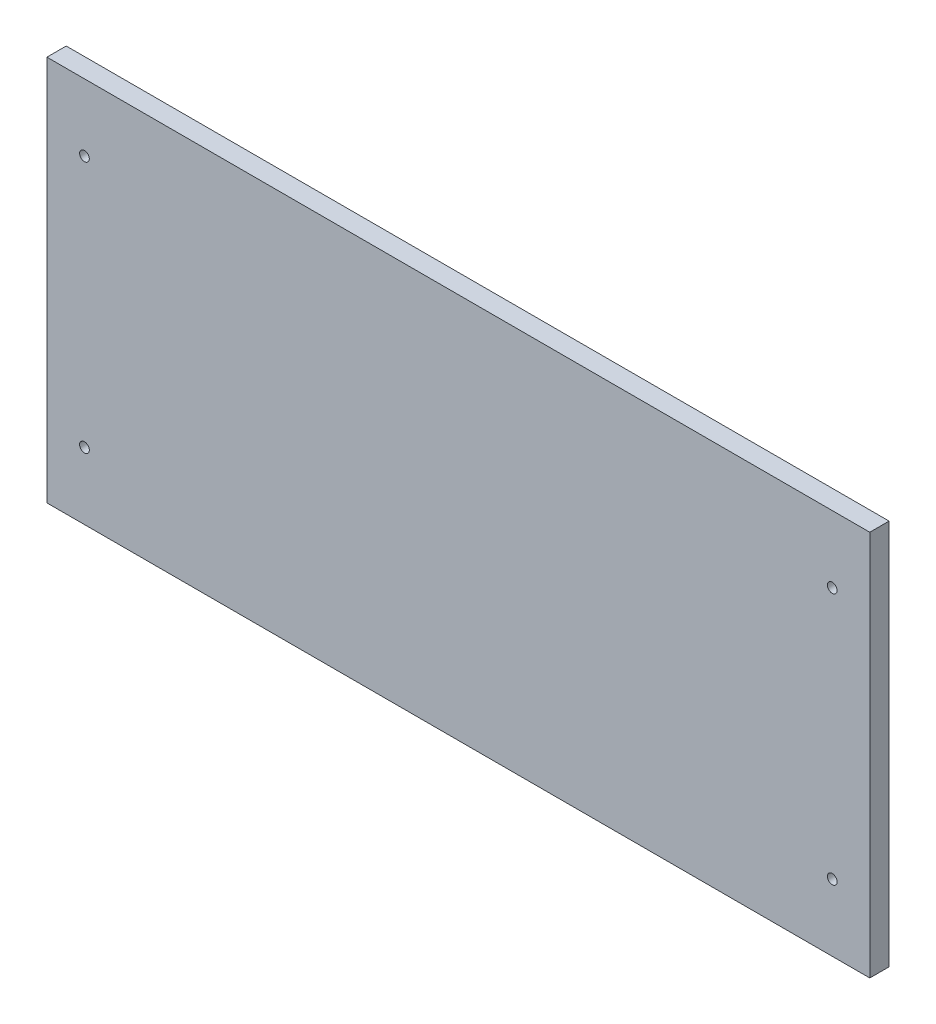
SolidWorks part; units mm, degrees
ref_plane "Front Plane" through (0, 0, 0) normal (0, 0, 1) x (1, 0, 0)
ref_plane "Top Plane" through (0, 0, 0) normal (0, 1, 0) x (1, 0, 0)
ref_plane "Right Plane" through (0, 0, 0) normal (1, 0, 0) x (0, 0, -1)
sketch "Sketch1" plane through (0, 0, 0) normal (0, 0, 1) x (1, 0, 0)
  line L0 (135.35, 127) -> (135.35, 0) construction
  line L1 (0, 0) -> (270.7, 0)
  line L2 (0, 0) -> (0, 127)
  line L3 (0, 127) -> (270.7, 127)
  line L4 (270.7, 0) -> (270.7, 127)
  line L5 (0, 63.5) -> (270.7, 63.5) construction
  circle A3 centre (12.35, 105) radius 1.6
  circle A7 centre (258.35, 105) radius 1.6
  circle A8 centre (258.35, 22) radius 1.6
  circle A9 centre (12.35, 22) radius 1.6
  dimension "D11" = 3.2
  dimension "D1" = 127
  dimension "D2" = 270.7
  dimension "D12" = 12.35
  dimension "D13" = 22
extrude "Wall" add sketch "Sketch1" along normal blind 6.35
sketch "Sketch2" plane through (0, 0, 6.35) normal (0, 0, 1) x (1, 0, 0)
  line L0 (135.35, 127) -> (135.35, 98.425) construction
  line L1 (270.7, 127) -> (0, 127) construction
  line L2 (135.35, 98.425) -> (66.6667, 98.425) construction
  line L3 (135.35, 98.425) -> (204.0333, 98.425) construction
  line L4 (0, 127) -> (0, 0) construction
  circle A0 centre (135.35, 98.425) radius 3.9687
  circle A1 centre (66.6667, 98.425) radius 3.9688
  circle A2 centre (204.0333, 98.425) radius 3.9687
  dimension "D2" = 7.9375
  dimension "D1" = 28.575
  dimension "D3" = 66.6667
extrude "RodSupportCutouts" [suppressed] cut sketch "Sketch2" against normal up to next
sketch "Sketch3" plane through (0, 0, 6.35) normal (0, 0, 1) x (1, 0, 0)
  line L1 (25.4, 88.9) -> (245.3, 88.9)
  line L2 (25.4, 88.9) -> (25.4, 114.3)
  line L3 (25.4, 114.3) -> (245.3, 114.3)
  line L4 (245.3, 88.9) -> (245.3, 114.3)
  line L5 (25.4, 88.9) -> (245.3, 114.3) construction
  line L6 (25.4, 114.3) -> (245.3, 88.9) construction
  line L7 (270.7, 127) -> (0, 127) construction
  line L8 (0, 127) -> (0, 0) construction
  point P0 (135.35, 101.6)
  point P9 (135.35, 127)
  dimension "D1" = 25.4
  dimension "D2" = 25.4
  dimension "D3" = 25.4
extrude "CannulaLargeCutout" [suppressed] cut sketch "Sketch3" against normal up to next
sketch "Sketch4" [suppressed] plane through (0, 0, 9.525) normal (0, 0, 1) x (1, 0, 0)
  line L0 (6, 103.5) -> (194, 103.5) construction
  line L1 (6, 105) -> (6, 22) construction
  line L2 (194, 105) -> (194, 22) construction
  line L3 (200, 127) -> (0, 127) construction
  line L4 (0, 127) -> (0, 0) construction
  circle A0 centre (60, 103.5) radius 6.35
  circle A1 centre (20, 103.5) radius 6.35
  circle A2 centre (100, 103.5) radius 6.35
  circle A3 centre (140, 103.5) radius 6.35
  circle A4 centre (60, 63.5) radius 6.35
  circle A5 centre (100, 63.5) radius 6.35
  circle A6 centre (140, 63.5) radius 6.35
  circle A7 centre (60, 23.5) radius 6.35
  circle A8 centre (100, 23.5) radius 6.35
  circle A9 centre (140, 23.5) radius 6.35
  circle A10 centre (20, 63.5) radius 6.35
  circle A11 centre (20, 23.5) radius 6.35
  circle A12 centre (180, 103.5) radius 6.35
  circle A13 centre (180, 63.5) radius 6.35
  circle A14 centre (180, 23.5) radius 6.35
  point P42 (100, 127)
  point P45 (0, 63.5)
  dimension "D3" = 12.7
  dimension "D1" = 5
  dimension "D2" = 3
extrude "CannulaHoles" [suppressed] cut sketch "Sketch4" against normal up to next
ref_plane "LeftBoundary" through (25.4, 0, 0) normal (-1, 0, 0) x (0, 0, 1)
ref_plane "RightBoundary" through (245.3, 0, 0) normal (1, 0, 0) x (0, 0, -1)
ref_plane "TopBoundary" through (0, 101.6, 0) normal (0, 1, 0) x (1, 0, 0)
ref_plane "BottomBoundary" through (0, 25.4, 0) normal (0, -1, 0) x (-1, 0, 0)
sketch "Sketch5" plane through (0, 0, 6.35) normal (0, 0, 1) x (1, 0, 0)
  line L4 (25.4, 3.4925) -> (25.4, -3.4925) construction
  line L5 (3.4925, 101.6) -> (-3.4925, 101.6) construction
  circle A0 centre (25.4, 101.6) radius 3.9687
  dimension "D1" = 7.9375
extrude "RodSupportCutout" cut sketch "Sketch5" along normal blind 3.35 from surface starting at face at (10.75, 22, 0)
pattern_linear "SupportPattern" count 7 spacing 36.65 along (1, 0, 0) count 5 spacing 19.05 along (0, -1, 0) of "RodSupportCutout"
equation "\"Length\"= 283mm"
equation "\"Width\"= 225mm"
equation "\"WallThickness\"= 0.25in"
equation "\"UpperWaterJacketThickness\"= 28mm"
equation "\"SpacerHeight\"= 80.2mm"
equation "\"SpacerCornerWidth\"= 10mm"
equation "\"SpacerCornerHeight\"= 60.16mm"
equation "\"SpacerPegDiameter\"= 10mm"
equation "\"SpacerPegHeight\"= 10mm"
equation "\"TubingShort\"= 110mm"
equation "\"TubingLong\"= 175mm"
equation "\"PlateLength\"= 252mm"
equation "\"PlateWidth\"= 190mm"
equation "\"PlateHoleDiameter\"= 5.9mm"
equation "\"PlateHoleBottom\"= 2mm"
equation "\"PlateHoleSide\"= 1.55mm"
equation "\"PlateHoleSpacing\"= 3.1mm"
equation "\"PlateThickness\"= 1.55mm"
equation "\"ReservoirBottom\"= 12.5mm"
equation "\"ReservoirSupportWidth\"= 12mm"
equation "\"ReservoirSupportHeight\"= 15.1mm"
equation "\"ReservoirSupportPlacementHeight\"= 50mm"
equation "\"ReservoirHoleDiameter\"= 12.7mm"
equation "\"ReservoirHoleRight\"= 25mm"
equation "\"ReservoirHoleTop\"= \"ReservoirSupportPlacementHeight\""
equation "\"ReservoirHeight\"= 90mm"
equation "\"ReservoirPortBottom\"= 4mm"
equation "\"ReservoirPortTop\"= 10mm"
equation "\"ReservoirPortWidth\"= 101mm"
equation "\"CustomSpacerHeight\"= 5in"
equation "\"CustomSpacerRodHoleHeight\"= .75in"
equation "\"CustomSpacerRodHoleDiameter\"= .3125in"
equation "\"ScrewBlockSide\"= 12mm"
equation "\"ScrewBlockUpperHeight\"= 16mm"
equation "\"ScrewBlockLowerHeight\"= 16mm"
equation "\"InternalLength\"= 258mm"
equation "\"InternalWidth\"= 200mm"
equation "\"CustomSpacerPegHeight\"= 1in"
equation "\"CustomSpacerScrewBore\"=3.2mm"
equation "\"CustomSpacerScrewDepth\"=10mm"
equation "\"D1@Sketch1\"=\"CustomSpacerHeight\""
equation "\"D2@Sketch1\"=\"WallLength\""
equation "\"D11@Sketch1\"=\"CustomSpacerScrewBore\""
equation "\"D12@Sketch1\"  = \"ScrewBlockSide\"/2 + \"WallThickness\""
equation "\"D13@Sketch1\"=\"ScrewBlockUpperHeight\"+\"ScrewBlockSide\"/2"
equation "\"D1@Wall\" = \"WallThickness\""
equation "\"D1@Sketch2\"=\"CustomSpacerRodHoleHeight\" + \"CustomSpacerRodHoleDiameter\" +0.0625in"
equation "\"D2@Sketch2\"=\"CustomSpacerRodHoleDiameter\""
equation "\"D3@Sketch2\"=\"InternalWidth\" / 3"
equation "\"D1@Sketch3\"=1in"
equation "\"WallLength\"= \"InternalLength\" + ( 2 * \"WallThickness\" )"
equation "\"D1@Sketch5\"=\"CustomSpacerRodHoleDiameter\""
equation "\"D1@RodSupportCutout\"=\"WallThickness\" - 3"
